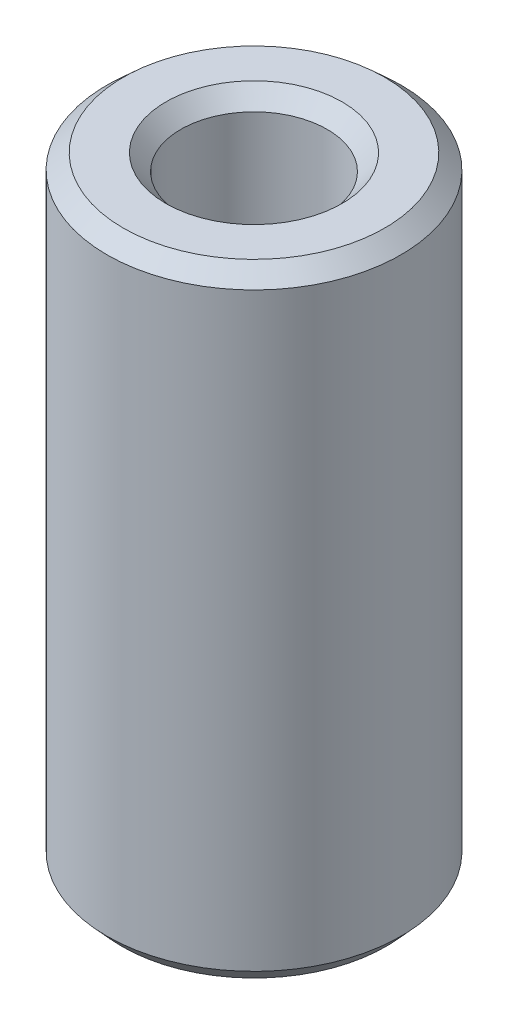
SolidWorks part; units mm, degrees
ref_plane "Front Plane" through (0, 0, 0) normal (0, 0, 1) x (1, 0, 0)
ref_plane "Top Plane" through (0, 0, 0) normal (0, 1, 0) x (1, 0, 0)
ref_plane "Right Plane" through (0, 0, 0) normal (1, 0, 0) x (0, 0, -1)
sketch "Sketch1" plane through (0, 0, 0) normal (0, 1, 0) x (1, 0, 0)
  circle A0 centre (0, 0) radius 5
  dimension "SLEEVE_OD" = 10
extrude "Boss-Extrude1" add sketch "Sketch1" along normal blind 21.1305
sketch "Sketch2" plane through (0, 0, 0) normal (0, 1, 0) x (1, 0, 0)
  circle A0 centre (0, 0) radius 2.4887
  dimension "BORE_D" = 4.9773
extrude "Cut-Extrude1" cut sketch "Sketch2" along normal through all
chamfer "Chamfer1" distance 0.5077 angle 47.587 4 edges at (0, 21.1305, 2.4887) (0, 0, 2.4887) (0, 0, 5) (0, 21.1305, 5) first distance on face at (0, 21.1305, 2.4887) first distance on face at (0, 0, 2.4887) first distance on face at (0, 21.1305, 5)
